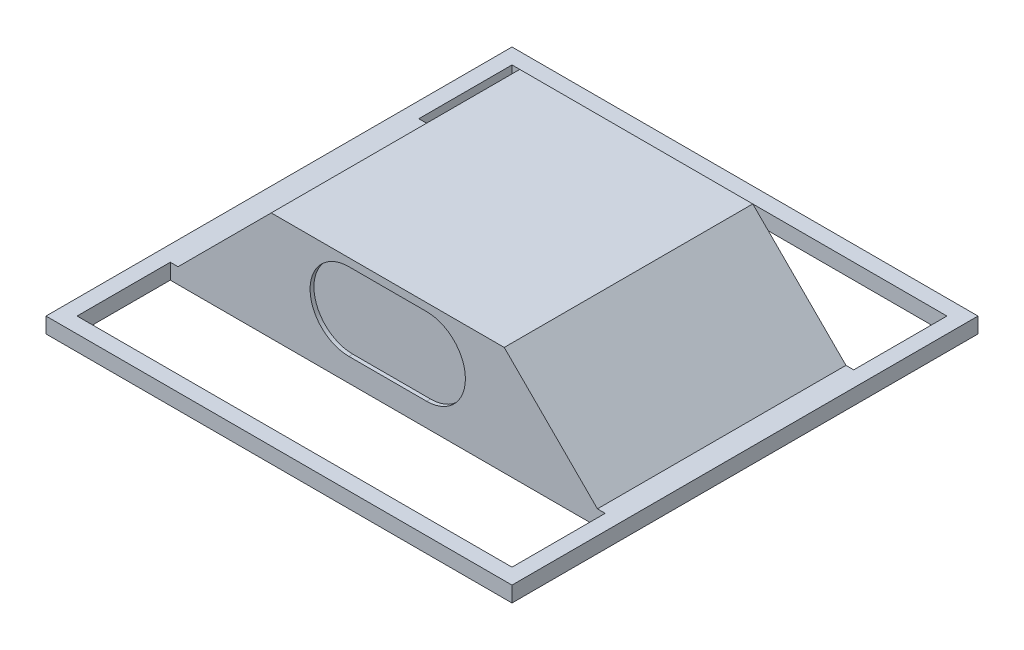
SolidWorks part; units mm, degrees
ref_plane "前视基准面" through (0, 0, 0) normal (0, 0, 1) x (1, 0, 0)
ref_plane "上视基准面" through (0, 0, 0) normal (0, 1, 0) x (1, 0, 0)
ref_plane "右视基准面" through (0, 0, 0) normal (1, 0, 0) x (0, 0, -1)
sketch "草图1" plane through (0, 0, 0) normal (0, 1, 0) x (1, 0, 0)
  line L9 (-300, -300) -> (-300, 300)
  line L10 (-280, 160) -> (-280, 280)
  line L14 (-55, 0) -> (55, 0) construction
  line L20 (-280, 280) -> (280, 280)
  line L21 (-300, -300) -> (300, -300)
  line L22 (-300, 300) -> (300, 300)
  line L23 (300, -300) -> (300, 300)
  line L24 (-280, 160) -> (280, 160)
  line L25 (280, 160) -> (280, 280)
  line L26 (-280, -160) -> (280, -160)
  line L27 (-280, -160) -> (-280, -280)
  line L28 (-280, -280) -> (280, -280)
  line L29 (280, -160) -> (280, -280)
  point P15 (-300, 0)
extrude "凸台-拉伸1" add sketch "草图1" along normal blind 20
sketch "草图2" plane through (0, 0, 160) normal (0, 0, 1) x (1, 0, 0)
  line L0 (-270, 20) -> (-270, 0)
  line L1 (-300, 20) -> (300, 20) construction
  line L2 (-300, 0) -> (300, 0) construction
  line L3 (150, 140) -> (-150, 140)
  line L4 (-150, 140) -> (-270, 20)
  line L5 (150, 140) -> (270, 20)
  line L6 (-270, 0) -> (270, 0)
  line L7 (270, 0) -> (270, 20)
extrude "凸台-拉伸2" add sketch "草图2" against normal blind 320
sketch "草图3" plane through (0, 0, 160) normal (0, 0, 1) x (1, 0, 0)
  line L3 (50, 130) -> (-50, 130)
  line L4 (50, 30) -> (-50, 30)
  arc A1 (-50, 130) -> (-50, 30) centre (-50, 80) ccw
  arc A2 (50, 130) -> (50, 30) centre (50, 80) cw
extrude "切除-拉伸1" cut sketch "草图3" against normal blind 5
extrude "切除-拉伸3" cut sketch "草图3<3>" along normal blind 5 from surface starting at face at (0, 45, -160)
sketch "草图3<3>" plane through (0, 0, 160) normal (0, 0, 1) x (1, 0, 0) same geometry as "草图3"
